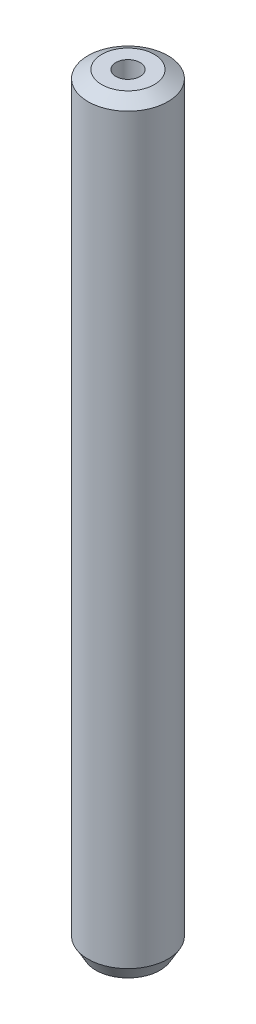
SolidWorks part; units mm, degrees
ref_plane "Front Plane" through (0, 0, 0) normal (0, 0, 1) x (1, 0, 0)
ref_plane "Top Plane" through (0, 0, 0) normal (0, 1, 0) x (1, 0, 0)
ref_plane "Right Plane" through (0, 0, 0) normal (1, 0, 0) x (0, 0, -1)
sketch "Sketch1" plane through (0, 0, 0) normal (0, 1, 0) x (1, 0, 0)
  circle A0 centre (0, 0) radius 27.5
  dimension "SHAFT_OD" = 55
extrude "Boss-Extrude1" add sketch "Sketch1" along normal blind 526.1496
sketch "Sketch2" plane through (0, 0, 0) normal (0, 1, 0) x (1, 0, 0)
  circle A0 centre (0, 0) radius 8.3563
  dimension "BORE_D" = 16.7127
extrude "Cut-Extrude1" cut sketch "Sketch2" along normal through all
chamfer "Chamfer1" distance 5.4468 angle 60 2 edges at (0, 526.1496, 27.5) (0, 0, 27.5) first distance on face at (0, 526.1496, 27.5) first distance on face at (0, 0, 8.3563)
